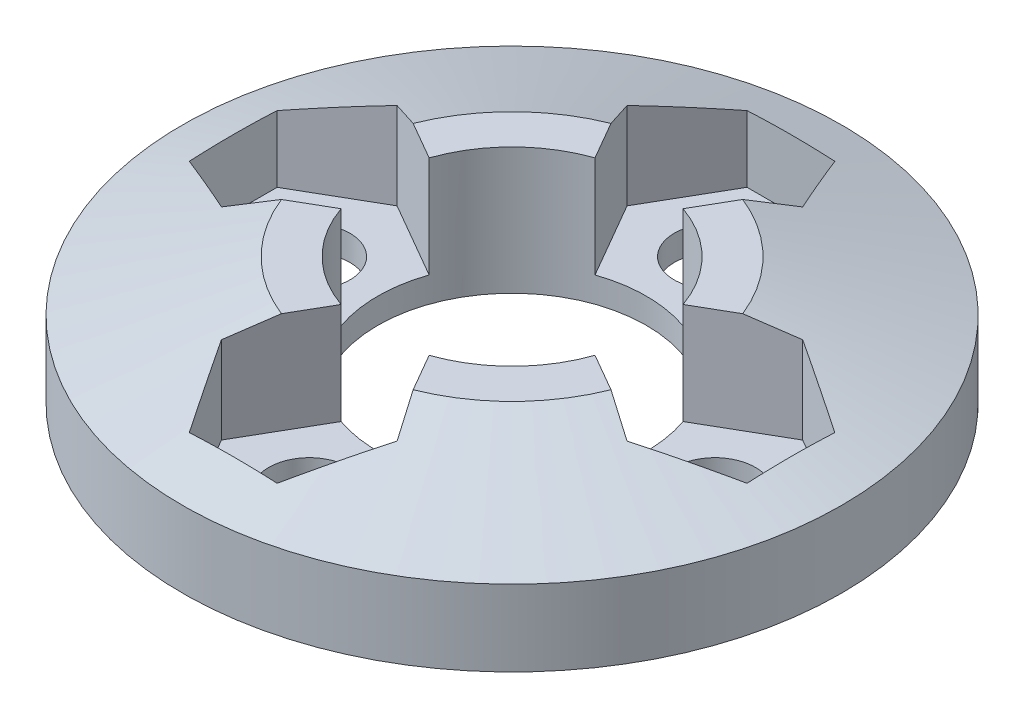
SolidWorks part; units mm, degrees
ref_plane "前视基准面" through (0, 0, 0) normal (0, 0, 1) x (1, 0, 0)
ref_plane "上视基准面" through (0, 0, 0) normal (0, 1, 0) x (1, 0, 0)
ref_plane "右视基准面" through (0, 0, 0) normal (1, 0, 0) x (0, 0, -1)
sketch "草图2" plane through (0, 0, 0) normal (0, 0, 1) x (1, 0, 0)
  line L0 (0, 0) -> (-13, 0)
  line L1 (-13, 0) -> (-13, 3)
  line L2 (-13, 3) -> (-7, 5)
  line L15 (0, 0) -> (0, 1.5)
  line L16 (-5.3, 5) -> (-7, 5)
  line L18 (-5.3, 3) -> (-5.3, 5)
  line L19 (-5.3, 3) -> (0, 3)
  line L20 (0, 3) -> (0, 1.5)
  dimension "D2" = 5.3
  dimension "D3" = 13
  dimension "D5" = 3
  dimension "D8" = 3
  dimension "D1" = 5
revolve "旋转1" add sketch "草图2" angle 360 about L15
ref_axis "基准轴1" through (0, 5, 0) along (0, -1, 0)
ref_plane "基准面1" through (0, 5.5, 0) normal (0, -1, 0) x (-1, 0, 0)
sketch "草图5" plane through (0, 5.5, 0) normal (0, -1, 0) x (-1, 0, 0)
  line L0 (8, -3.4641) -> (11, -1.7321)
  line L1 (3.4641, 8) -> (1.7321, 11)
  line L2 (1.7321, 11) -> (-1.7321, 11)
  line L3 (-1.7321, 11) -> (-3.4641, 8)
  line L4 (-3.4641, 8) -> (-1.7321, 5)
  line L5 (-1.7321, 5) -> (1.7321, 5)
  line L6 (1.7321, 5) -> (3.4641, 8)
  line L7 (11, -1.7321) -> (11, 1.7321)
  line L8 (11, 1.7321) -> (8, 3.4641)
  line L9 (8, 3.4641) -> (5, 1.7321)
  line L10 (5, 1.7321) -> (5, -1.7321)
  line L11 (5, -1.7321) -> (8, -3.4641)
  line L12 (-3.4641, -8) -> (-1.7321, -11)
  line L13 (-1.7321, -11) -> (1.7321, -11)
  line L14 (1.7321, -11) -> (3.4641, -8)
  line L15 (3.4641, -8) -> (1.7321, -5)
  line L16 (1.7321, -5) -> (-1.7321, -5)
  line L17 (-1.7321, -5) -> (-3.4641, -8)
  line L18 (-8, 3.4641) -> (-11, 1.7321)
  line L19 (-11, 1.7321) -> (-11, -1.7321)
  line L20 (-11, -1.7321) -> (-8, -3.4641)
  line L21 (-8, -3.4641) -> (-5, -1.7321)
  line L22 (-5, -1.7321) -> (-5, 1.7321)
  line L23 (-5, 1.7321) -> (-8, 3.4641)
  circle A0 centre (0, 8) radius 3 construction
  point P1 (0, 0)
  point P30 (0, 0)
  dimension "D1" = 6
  dimension "D3" = 8
  dimension "D2" = 4
extrude "切除-拉伸1" cut sketch "草图5" along normal offset from surface 1 and the other way blind 3.5 up to face at (13, 0, 0)
sketch "草图6" plane through (0, 5.5, 0) normal (0, -1, 0) x (-1, 0, 0)
  circle A0 centre (0, 8) radius 1.6
  circle A1 centre (8, 0) radius 1.6
  circle A2 centre (0, -8) radius 1.6
  circle A3 centre (-8, 0) radius 1.6
  point P3 (0, 0)
  point P12 (0, 0)
  dimension "D1" = 3.2
  dimension "D2" = 4
extrude "切除-拉伸2" cut sketch "草图6" along normal through all
sketch "草图8" plane through (0, 5.5, 0) normal (0, -1, 0) x (-1, 0, 0)
  circle A0 centre (0, 0) radius 5.3
  dimension "D1" = 10.6
extrude "切除-拉伸3" cut sketch "草图8" along normal blind 10
